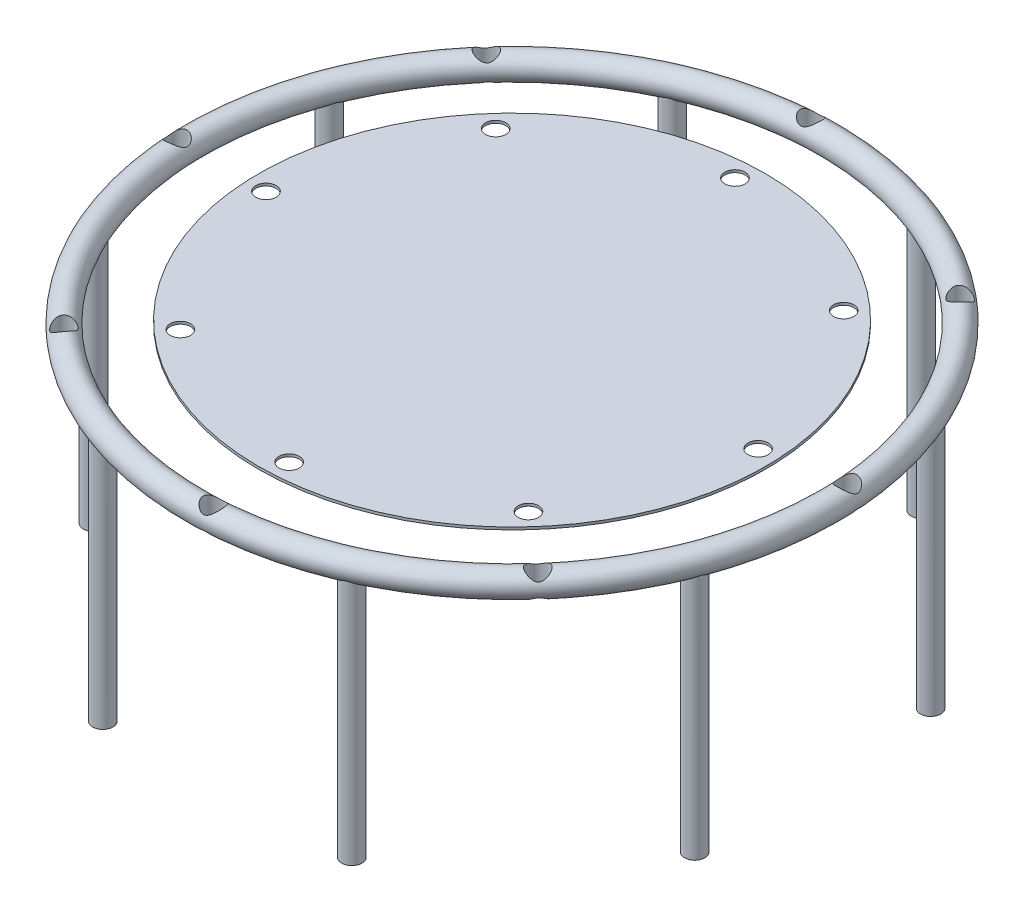
SolidWorks part; units mm, degrees
note: '?' marks a value the reader was unsure of.
ref_plane "Front Plane" through (0, 0, 0) normal (0, 0, 1) x (1, 0, 0)
ref_plane "Top Plane" through (0, 0, 0) normal (0, 1, 0) x (1, 0, 0)
ref_plane "Right Plane" through (0, 0, 0) normal (1, 0, 0) x (0, 0, -1)
sketch "Sketch1" plane through (0, 0, 0) normal (0, 1, 0) x (1, 0, 0)
  circle A0 centre (0, 0) radius 1250
  dimension "D1" = 2500
sweep "Sweep1" add path "Sketch1" circular profile diameter 100 parameters "D3"=100
ref_plane "Plane1" through (0, 50, 0) normal (0, 1, 0) x (1, 0, 0)
sketch "Sketch17" plane through (0, 50, 0) normal (0, 1, 0) x (1, 0, 0)
  circle A0 centre (-1250, -71.8055) radius 40
  dimension "D2" = 80
  dimension "D1" = 1250
extrude "Cut-Extrude7" cut sketch "Sketch17" against normal blind 100
ref_axis "Axis1" through (-1250, -50, 71.8055) along (0, 1, 0)?
sketch "Sketch18" plane through (0, 50, 0) normal (0, 1, 0) x (1, 0, 0)
  line L0 (-997.8906, 0) -> (1200, 0) construction
  line L1 (0, 1200) -> (0, -1200) construction
  circle A1 centre (0, 0) radius 1200 construction
  point P3 (-997.8906, 64.9185)
ref_point "Point1"
ref_axis "Axis4" through (0, 0, 1250) along (0, 0.04, -0.9992)?
sketch "Sketch19" plane through (0, 0, 0) normal (1, 0, 0) x (0, 0, -1)
  line L0 (0, 50) -> (0, -337.1845) construction
  line L1 (1200, 50) -> (-1200, 50) construction
ref_axis "Axis5" through (0, 707.7046, 0) along (0, -1, 0)?
pattern_circular "CirPattern2" count 8 over 360 about axis through (0, 0, 0) along (0, 1, 0) of "Cut-Extrude7"
sketch "Sketch21" plane through (0, 0, 0) normal (0, 1, 0) x (1, 0, 0)
  circle A0 centre (0, 0) radius 1000
  dimension "D1" = 2000
extrude "Boss-Extrude1" add sketch "Sketch21" along normal blind 10 separate body contours A0
sketch "Sketch24" plane through (0, 10, 0) normal (0, 1, 0) x (1, 0, 0)
  circle A0 centre (-925, -45.6944) radius 40
  dimension "D2" = 80
  dimension "D1" = 925
ref_axis "Axis6" through (-1250, -50, 71.8055) along (0, 1, 0)?
extrude "Cut-Extrude8" cut sketch "Sketch24" against normal blind 10
pattern_circular "CirPattern13" count 8 over 360 about axis through (0, 0, 0) along (0, 1, 0) of "Cut-Extrude8"
sketch "Sketch26" plane through (0, 0, 0) normal (0, 1, 0) x (1, 0, 0)
  circle A0 centre (-1167.3969, 446.8607) radius 40
  point P2 (0, 0)
  dimension "D1" = 80
  dimension "D2" = 1250
extrude "Boss-Extrude2" add sketch "Sketch26" against normal blind 1000
pattern_circular "CirPattern14" count 8 over 360 about axis through (0, 0, 0) along (0, 1, 0) of "Boss-Extrude2"
